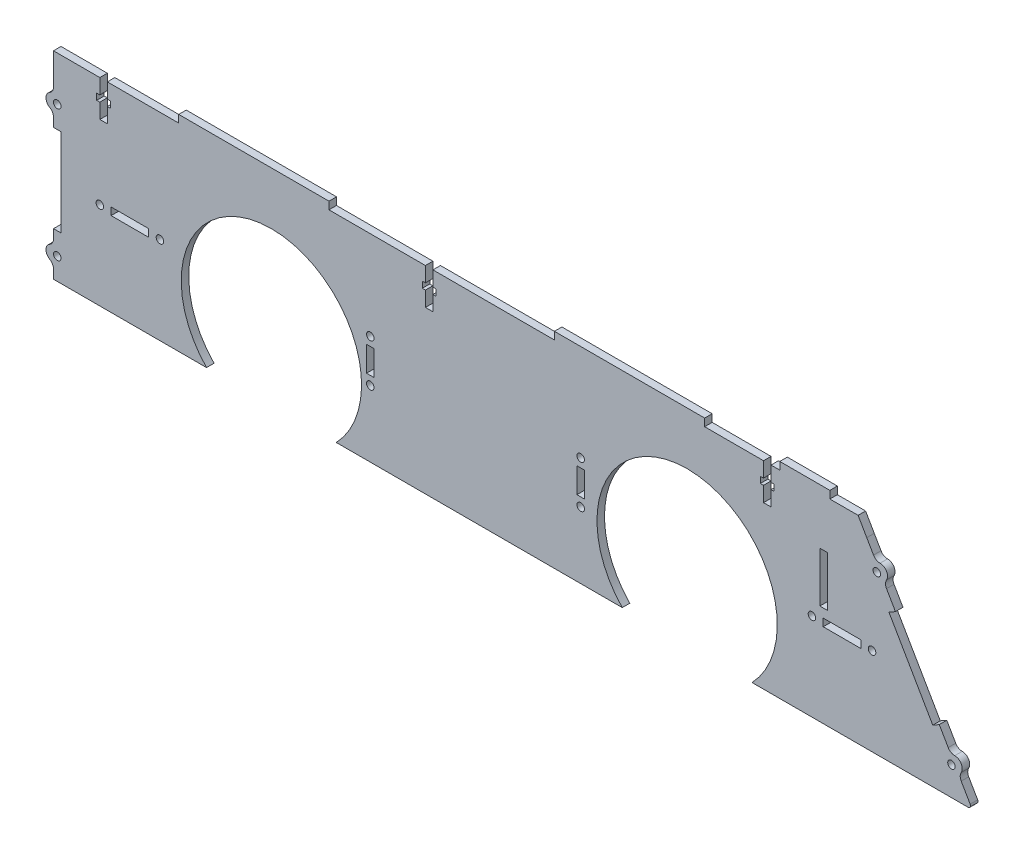
SolidWorks part; units mm, degrees
ref_plane "Спереди" through (0, 0, 0) normal (0, 0, 1) x (1, 0, 0)
ref_plane "Сверху" through (0, 0, 0) normal (0, 1, 0) x (1, 0, 0)
ref_plane "Справа" through (0, 0, 0) normal (1, 0, 0) x (0, 0, -1)
sketch "Эскиз1" plane through (0, 0, 0) normal (0, 0, 1) x (1, 0, 0)
  line L5 (-42.1466, 73) -> (0, 0)
  line L6 (-366.8766, 73) -> (-42.1466, 73)
  line L7 (-366.8766, 0) -> (-366.8766, 73)
  line L8 (0, 0) -> (-366.8766, 0)
  dimension "D1" = 60
  dimension "D2" = 73
  dimension "D3" = 324.73
  dimension "D4" = 84.2931
extrude "Бобышка-Вытянуть1" add sketch "Эскиз1" along normal blind 3
sketch "Эскиз2" plane through (0, 0, 3) normal (0, 0, 1) x (1, 0, 0)
  line L0 (-366.8766, 73) -> (-366.8766, 0) construction
  line L1 (-366.8766, 52.5) -> (-363.8766, 52.5)
  line L2 (-366.8766, 52.5) -> (-366.8766, 17.5)
  line L3 (-366.8766, 17.5) -> (-363.8766, 17.5)
  line L4 (-363.8766, 52.5) -> (-363.8766, 17.5)
  point P6 (-366.8766, 35)
  dimension "D1" = 35
  dimension "D2" = 3
  dimension "D3" = 35
extrude "Вырез-Вытянуть1" cut sketch "Эскиз2" against normal blind 3
sketch "Эскиз3" plane through (0, 0, 3) normal (0, 0, 1) x (1, 0, 0)
  line L0 (-33.2874, 51.6554) -> (-30.6893, 53.1554)
  line L1 (-33.2874, 51.6554) -> (-15.7874, 21.3446)
  line L2 (-30.6893, 53.1554) -> (-13.1893, 22.8446)
  line L3 (-15.7874, 21.3446) -> (-13.1893, 22.8446)
  line L4 (-45.6107, 73) -> (-3.4641, 0) construction
  line L5 (-42.1466, 73) -> (-366.8766, 73) construction
  line L9 (0, 0) -> (-42.1466, 73) construction
  line L10 (-366.8766, 0) -> (0, 0) construction
  line L11 (0, 0) -> (-42.1466, 73) construction
  point P12 (-24.5374, 36.5)
  point P13 (-24.5374, 36.5)
  dimension "D1" = 35
  dimension "D2" = 3
extrude "Вырез-Вытянуть2" cut sketch "Эскиз3" against normal blind 3
sketch "Эскиз4" plane through (0, 0, 3) normal (0, 0, 1) x (1, 0, 0)
  line L0 (-366.8766, 0) -> (0, 0) construction
  line L1 (-241.8766, 40) -> (-238.8766, 40)
  line L2 (-241.8766, 40) -> (-241.8766, 30)
  line L3 (-241.8766, 30) -> (-238.8766, 30)
  line L4 (-238.8766, 40) -> (-238.8766, 30)
  line L5 (-241.8766, 40) -> (-238.8766, 30) construction
  line L6 (-241.8766, 30) -> (-238.8766, 40) construction
  line L7 (-157.8766, 40) -> (-154.8766, 40)
  line L8 (-157.8766, 40) -> (-157.8766, 30)
  line L9 (-157.8766, 30) -> (-154.8766, 30)
  line L10 (-154.8766, 40) -> (-154.8766, 30)
  line L11 (-157.8766, 40) -> (-154.8766, 30) construction
  line L12 (-157.8766, 30) -> (-154.8766, 40) construction
  point P0 (-240.3766, 35)
  point P5 (-156.3766, 35)
  dimension "D1" = 3
  dimension "D2" = 10
  dimension "D3" = 84
  dimension "D4" = 123.5
  dimension "D5" = 35
extrude "Вырез-Вытянуть3" cut sketch "Эскиз4" against normal blind 3
sketch "Эскиз5" plane through (0, 0, 3) normal (0, 0, 1) x (1, 0, 0)
  line L1 (-343.8766, 36.5) -> (-328.8766, 36.5)
  line L2 (-343.8766, 36.5) -> (-343.8766, 33.5)
  line L3 (-343.8766, 33.5) -> (-328.8766, 33.5)
  line L4 (-328.8766, 36.5) -> (-328.8766, 33.5)
  line L5 (-343.8766, 36.5) -> (-328.8766, 33.5) construction
  line L6 (-343.8766, 33.5) -> (-328.8766, 36.5) construction
  line L7 (-59.5366, 36.5) -> (-44.5366, 36.5)
  line L8 (-59.5366, 36.5) -> (-59.5366, 33.5)
  line L9 (-59.5366, 33.5) -> (-44.5366, 33.5)
  line L10 (-44.5366, 36.5) -> (-44.5366, 33.5)
  line L11 (-59.5366, 36.5) -> (-44.5366, 33.5) construction
  line L12 (-59.5366, 33.5) -> (-44.5366, 36.5) construction
  point P0 (-336.3766, 35)
  point P5 (-52.0366, 35)
  dimension "D1" = 15
  dimension "D2" = 3
  dimension "D3" = 27.5
  dimension "D4" = 284.34
  dimension "D5" = 35
extrude "Вырез-Вытянуть4" cut sketch "Эскиз5" against normal blind 3
sketch "Эскиз6" plane through (0, 73, 0) normal (0, 1, 0) x (1, 0, 0)
  line L0 (-42.1466, -3) -> (-366.8766, -3) construction
  line L1 (-366.8766, 0) -> (-42.1466, 0)
  line L2 (-366.8766, 0) -> (-366.8766, -3)
  line L3 (-366.8766, -3) -> (-42.1466, -3)
  line L4 (-42.1466, 0) -> (-42.1466, -3)
extrude "Бобышка-Вытянуть2" add sketch "Эскиз6" along normal blind 6
sketch "Эскиз7" plane through (0, 0, 3) normal (0, 0, 1) x (1, 0, 0)
  line L0 (-366.8766, 17.5) -> (-366.8766, 0) construction
  line L1 (-363.8766, 35) -> (-385.1167, 35) construction
  line L2 (-363.8766, 17.5) -> (-363.8766, 52.5) construction
  circle A0 centre (-365.3766, 8.75) radius 1.5
  circle A1 centre (-365.3766, 61.25) radius 1.5
  point P5 (-366.8766, 8.75)
  dimension "D1" = 3
  dimension "D2" = 1.5
sketch "Эскиз8" plane through (-366.8766, 0, 0) normal (-1, 0, 0) x (0, 0, 1)
  line L0 (0, 17.5) -> (0, 0) construction
  line L1 (0, 8.75) -> (3, 8.75)
  line L2 (0, 8.75) -> (0, 5.75)
  line L3 (0, 5.75) -> (3, 5.75)
  line L4 (3, 8.75) -> (3, 5.75)
  line L5 (3, 17.5) -> (3, 0) construction
  dimension "D1" = 3
revolve "Повернуть1" add sketch "Эскиз8" angle 360 about L1
sketch "Эскиз9" plane through (-366.8766, 0, 0) normal (-1, 0, 0) x (0, 0, 1)
  line L0 (0, 79) -> (0, 52.5) construction
  line L1 (0, 61.25) -> (3, 61.25)
  line L2 (0, 61.25) -> (0, 58.25)
  line L3 (0, 58.25) -> (3, 58.25)
  line L4 (3, 61.25) -> (3, 58.25)
  line L5 (3, 79) -> (3, 52.5) construction
  dimension "D1" = 3
  dimension "D2" = 8.75
revolve "Повернуть2" add sketch "Эскиз9" angle 360 about L1
extrude "Вырез-Вытянуть6" cut sketch "Эскиз7" against normal blind 3
fillet "Скругление1" radius 3 4 edges at (-366.8766, 11.75, 1.5) (-366.8766, 5.75, 1.5) (-366.8766, 58.25, 1.5) (-366.8766, 64.25, 1.5)
sketch "Эскиз14" plane through (0, 0, 3) normal (0, 0, 1) x (1, 0, 0)
  line L0 (-154.8766, 40) -> (-157.8766, 40) construction
  line L1 (-157.8766, 30) -> (-154.8766, 30) construction
  line L2 (-241.8766, 30) -> (-238.8766, 30) construction
  circle A0 centre (-156.3766, 43.5) radius 1.5
  circle A1 centre (-156.3766, 26.5) radius 1.5
  circle A2 centre (-240.3766, 26.5) radius 1.5
  circle A3 centre (-240.3766, 43.5) radius 1.5
  point P11 (-156.3766, 40)
  point P20 (-240.3766, 30)
  dimension "D1" = 3
  dimension "D2" = 3.5
  dimension "D3" = 3.5
extrude "Вырез-Вытянуть9" cut sketch "Эскиз14" against normal blind 3
sketch "Эскиз15" plane through (0, 0, 3) normal (0, 0, 1) x (1, 0, 0)
  line L0 (-59.5366, 36.5) -> (-59.5366, 33.5) construction
  line L1 (-44.5366, 33.5) -> (-44.5366, 36.5) construction
  line L2 (-343.8766, 36.5) -> (-343.8766, 33.5) construction
  line L3 (-328.8766, 33.5) -> (-328.8766, 36.5) construction
  circle A0 centre (-324.3766, 35) radius 1.5
  circle A1 centre (-348.3766, 35) radius 1.5
  circle A2 centre (-64.0366, 35) radius 1.5
  circle A3 centre (-40.0366, 35) radius 1.5
  point P16 (-59.5366, 35)
  dimension "D1" = 3
  dimension "D2" = 4.5
  dimension "D3" = 4.5
  dimension "D4" = 4.5
  dimension "D5" = 4.5
extrude "Вырез-Вытянуть10" cut sketch "Эскиз15" against normal blind 3
sketch "Эскиз16" plane through (0, 0, 0) normal (0.866, 0.5, 0) x (0, 0, -1)
  line L0 (-3, 0) -> (-3, 26.3786) construction
  line L1 (-3, 11.0586) -> (0, 11.0586)
  line L2 (-3, 11.0586) -> (-3, 14.0586)
  line L3 (-3, 14.0586) -> (0, 14.0586)
  line L4 (0, 11.0586) -> (0, 14.0586)
  line L5 (0, 0) -> (0, 26.3786) construction
  dimension "D1" = 3
  dimension "D2" = 12.32
revolve "Повернуть3" add sketch "Эскиз16" angle 360 about L3
sketch "Эскиз17" plane through (0, 0, 0) normal (0.866, 0.5, 0) x (0, 0, -1)
  line L0 (-3, 61.3786) -> (-3, 84.2931) construction
  line L1 (-3, 73.6986) -> (0, 73.6986)
  line L2 (-3, 73.6986) -> (-3, 76.6986)
  line L3 (-3, 76.6986) -> (0, 76.6986)
  line L4 (0, 73.6986) -> (0, 76.6986)
  line L5 (0, 61.3786) -> (0, 84.2931) construction
  dimension "D1" = 3
  dimension "D2" = 12.32
revolve "Повернуть4" add sketch "Эскиз17" angle 360 about L1
sketch "Эскиз18" plane through (0, 0, 3) normal (0, 0, 1) x (1, 0, 0)
  line L1 (-15.7874, 21.3446) -> (-3.4641, 0) construction
  line L2 (0, 0) -> (-5.5293, 9.577) construction
  line L3 (-366.8766, 0) -> (0, 0) construction
  line L5 (-9.6257, 10.6723) -> (-6.0018, 12.7646) construction
  circle A0 centre (-38.15, 63.0777) radius 1.5
  circle A1 centre (-8.3267, 11.4223) radius 1.5
  dimension "D1" = 3
  dimension "D2" = 3
  dimension "D3" = 9.9223
  dimension "D4" = 1.5
  dimension "D5" = 7.4607
extrude "Вырез-Вытянуть11" cut sketch "Эскиз18" against normal blind 3
fillet "Скругление2" radius 3 4 edges at (-38.3493, 66.423, 1.5) (-35.3493, 61.2268, 1.5) (-8.5293, 14.7732, 1.5) (-5.5293, 9.577, 1.5)
chamfer "Фаска1" distance 6 angle 30 1 edges at (-42.1466, 79, 1.5) first distance on face at (-42.1466, 76, 1.5)
sketch "Эскиз19" plane through (0, 0, 3) normal (0, 0, 1) x (1, 0, 0)
  line L0 (-366.8766, 0) -> (0, 0) construction
  line L1 (-363.8766, 17.5) -> (-363.8766, 52.5) construction
  circle A0 centre (-279.8766, 25) radius 36
  circle A1 centre (-113.8766, 25) radius 36
  dimension "D4" = 72
  dimension "D1" = 25
  dimension "D2" = 166
  dimension "D3" = 84
extrude "Вырез-Вытянуть12" cut sketch "Эскиз19" against normal blind 3
sketch "Эскиз24" plane through (0, 79, 0) normal (0, 1, 0) x (1, 0, 0)
  line L0 (-366.8766, -3) -> (-45.6107, -3) construction
  line L1 (-56.8766, -3) -> (-76.8766, -3)
  line L2 (-56.8766, -3) -> (-56.8766, 0)
  line L3 (-56.8766, 0) -> (-76.8766, 0)
  line L4 (-76.8766, -3) -> (-76.8766, 0)
  line L5 (-45.6107, 0) -> (-366.8766, 0) construction
  line L7 (-106.8766, -3) -> (-166.8766, -3)
  line L8 (-106.8766, -3) -> (-106.8766, 0)
  line L9 (-106.8766, 0) -> (-166.8766, 0)
  line L10 (-166.8766, -3) -> (-166.8766, 0)
  line L11 (-316.8766, -3) -> (-256.8766, -3)
  line L12 (-316.8766, -3) -> (-316.8766, 0)
  line L13 (-316.8766, 0) -> (-256.8766, 0)
  line L14 (-256.8766, -3) -> (-256.8766, 0)
  dimension "D1" = 50
  dimension "D2" = 60
  dimension "D3" = 60
  dimension "D4" = 200
  dimension "D5" = 20
  dimension "D6" = 290
extrude "Бобышка-Вытянуть3" add sketch "Эскиз24" along normal blind 3
sketch "Эскиз25" plane through (0, 0, 3) normal (0, 0, 1) x (1, 0, 0)
  line L0 (-348.3766, 79) -> (-348.3766, 73)
  line L1 (-348.3766, 73) -> (-349.6266, 73)
  line L2 (-349.6266, 73) -> (-349.6266, 70.5)
  line L3 (-349.6266, 70.5) -> (-348.3766, 70.5)
  line L4 (-348.3766, 70.5) -> (-348.3766, 64.5)
  line L5 (-348.3766, 64.5) -> (-345.3766, 64.5)
  line L6 (-345.3766, 64.5) -> (-345.3766, 70.5)
  line L7 (-345.3766, 70.5) -> (-344.1266, 70.5)
  line L8 (-344.1266, 70.5) -> (-344.1266, 73)
  line L9 (-344.1266, 73) -> (-345.3766, 73)
  line L10 (-345.3766, 73) -> (-345.3766, 79)
  line L11 (-345.3766, 79) -> (-348.3766, 79)
  line L12 (-218.3766, 79) -> (-218.3766, 73)
  line L13 (-218.3766, 73) -> (-219.6266, 73)
  line L14 (-219.6266, 73) -> (-219.6266, 70.5)
  line L15 (-219.6266, 70.5) -> (-218.3766, 70.5)
  line L16 (-218.3766, 70.5) -> (-218.3766, 64.5)
  line L17 (-218.3766, 64.5) -> (-215.3766, 64.5)
  line L18 (-215.3766, 64.5) -> (-215.3766, 70.5)
  line L19 (-215.3766, 70.5) -> (-214.1266, 70.5)
  line L20 (-214.1266, 70.5) -> (-214.1266, 73)
  line L21 (-214.1266, 73) -> (-215.3766, 73)
  line L22 (-215.3766, 73) -> (-215.3766, 79)
  line L23 (-215.3766, 79) -> (-218.3766, 79)
  line L24 (-83.3766, 79) -> (-83.3766, 73)
  line L25 (-83.3766, 73) -> (-84.6266, 73)
  line L26 (-84.6266, 73) -> (-84.6266, 70.5)
  line L27 (-84.6266, 70.5) -> (-83.3766, 70.5)
  line L28 (-83.3766, 70.5) -> (-83.3766, 64.5)
  line L29 (-83.3766, 64.5) -> (-80.3766, 64.5)
  line L30 (-80.3766, 64.5) -> (-80.3766, 70.5)
  line L31 (-80.3766, 70.5) -> (-79.1266, 70.5)
  line L32 (-79.1266, 70.5) -> (-79.1266, 73)
  line L33 (-79.1266, 73) -> (-80.3766, 73)
  line L34 (-80.3766, 73) -> (-80.3766, 79)
  line L35 (-80.3766, 79) -> (-83.3766, 79)
  line L36 (-366.8766, 79) -> (-316.8766, 79) construction
  line L37 (-256.8766, 79) -> (-166.8766, 79) construction
  line L38 (-106.8766, 79) -> (-76.8766, 79) construction
  point P42 (-346.8766, 79)
  point P47 (-216.8766, 79)
  point P54 (-81.8766, 79)
  dimension "D1" = 6
  dimension "D2" = 3
  dimension "D3" = 2.5
  dimension "D4" = 5.5
  dimension "D5" = 6
  dimension "D6" = 3
  dimension "D7" = 2.5
  dimension "D8" = 5.5
  dimension "D9" = 6
  dimension "D10" = 3
  dimension "D11" = 2.5
  dimension "D12" = 5.5
  dimension "D13" = 20
  dimension "D14" = 150
  dimension "D15" = 285
extrude "Вырез-Вытянуть13" cut sketch "Эскиз25" against normal blind 3
fillet "Скругление3" radius 1 1 edges at (0, 0, 1.5)
sketch "Эскиз26" plane through (0, 0, 3) normal (0, 0, 1) x (1, 0, 0)
  line L5 (-60.8766, 60) -> (-57.8766, 60)
  line L6 (-60.8766, 60) -> (-60.8766, 40)
  line L7 (-60.8766, 40) -> (-57.8766, 40)
  line L8 (-57.8766, 60) -> (-57.8766, 40)
  line L11 (-87.9729, 0) -> (-1.7321, 0) construction
  dimension "D1" = 3
  dimension "D2" = 20
  dimension "D3" = 40
  dimension "D4" = 306
extrude "Вырез-Вытянуть14" cut sketch "Эскиз26" against normal blind 3
